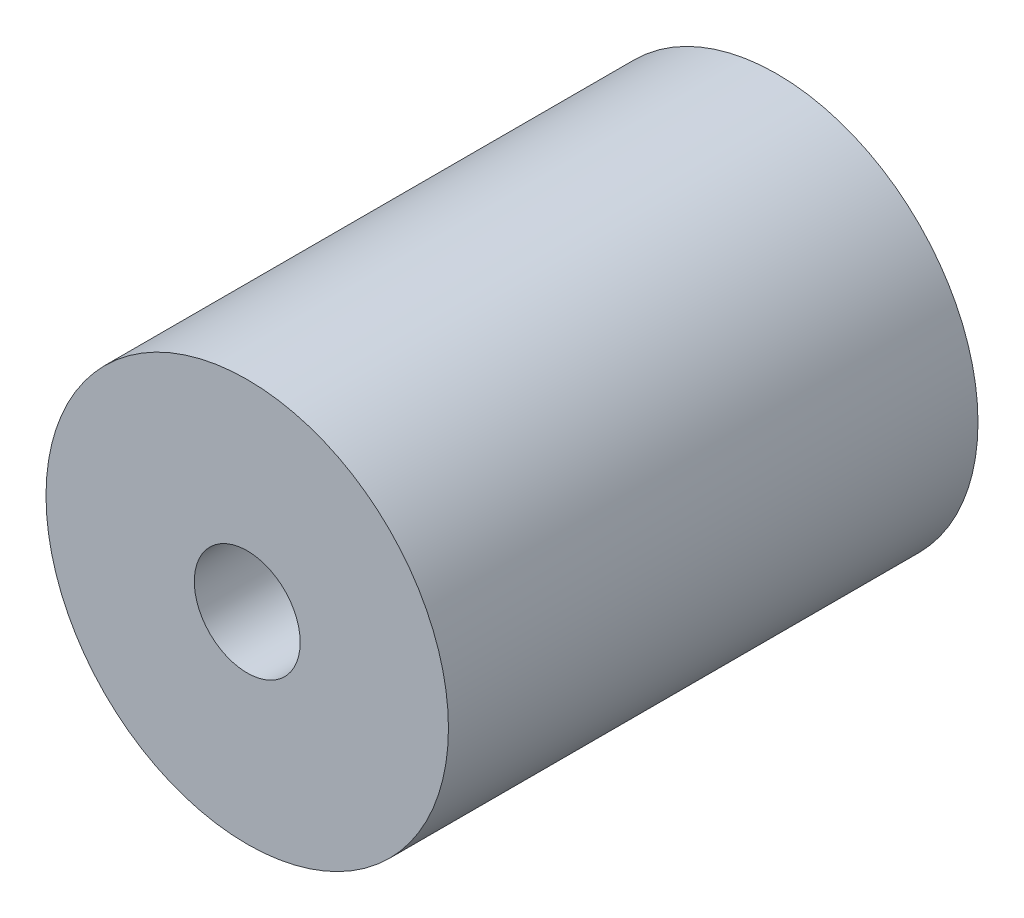
SolidWorks part; units mm, degrees
material "Cast Alloy Steel"
ref_plane "Front Plane" through (0, 0, 0) normal (0, 0, 1) x (1, 0, 0)
ref_plane "Top Plane" through (0, 0, 0) normal (0, 1, 0) x (1, 0, 0)
ref_plane "Right Plane" through (0, 0, 0) normal (1, 0, 0) x (0, 0, -1)
sketch "Sketch1" plane through (0, 0, 0) normal (0, 0, 1) x (1, 0, 0)
  circle A0 centre (0, 0) radius 4
  circle A1 centre (0, 0) radius 2.5
  circle A2 centre (0, 0) radius 9.5
  dimension "D1" = 5
  dimension "D2" = 8
  dimension "D3" = 19
extrude "Boss-Extrude1" add sketch "Sketch1" against normal blind 17.5 contours A2 A0 region at (-9.2313, 0, 0)
extrude "Boss-Extrude2" add sketch "Sketch1<3>" along normal blind 7.5 contours A0 A1 | A2 A0 region at (-3.8869, 0, 0) region at (-9.2313, 0, 0)
sketch "Sketch1<3>" plane through (0, 0, 0) normal (0, 0, 1) x (1, 0, 0) same geometry as "Sketch1"
